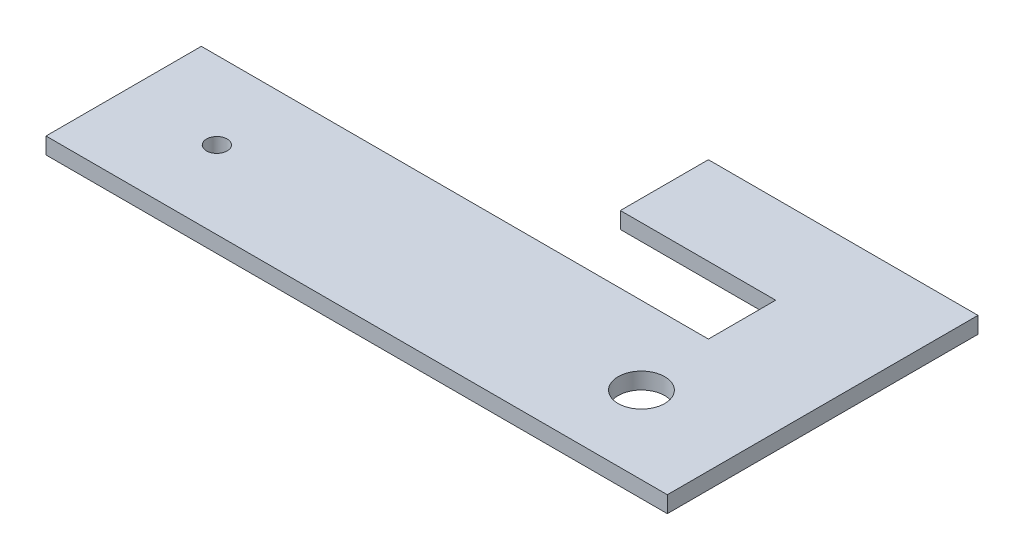
SolidWorks part; units mm, degrees
ref_plane "Front" through (0, 0, 0) normal (0, 0, 1) x (1, 0, 0)
ref_plane "Top" through (0, 0, 0) normal (0, 1, 0) x (1, 0, 0)
ref_plane "Right" through (0, 0, 0) normal (1, 0, 0) x (0, 0, -1)
sketch "Sketch1" plane through (0, 0, 0) normal (0, 1, 0) x (1, 0, 0)
  line L1 (0, 0) -> (120, 0)
  line L2 (0, 0) -> (0, 30)
  line L3 (0, 30) -> (120, 30)
  line L4 (120, 0) -> (120, 30)
  dimension "D1" = 120
  dimension "D2" = 30
extrude "Boss-Extrude1" add sketch "Sketch1" along normal blind 3.175
sketch "Sketch2" plane through (0, 3.175, 0) normal (0, 1, 0) x (1, 0, 0)
  line L0 (0, 30) -> (0, 0) construction
  line L1 (120, 30) -> (0, 30) construction
  line L2 (120, 0) -> (120, 30) construction
  circle A0 centre (18, 15) radius 2
  circle A1 centre (100, 15) radius 4.5
  dimension "D1" = 18
  dimension "D3" = 15
  dimension "D2" = 15
  dimension "D4" = 20
extrude "Cut-Extrude1" cut sketch "Sketch2" against normal blind 3.175
sketch "Sketch3" plane through (0, 0, -30) normal (0, 0, -1) x (-1, 0, 0)
  line L0 (-120, 0) -> (0, 0) construction
  line L1 (-97.9274, 0) -> (-120, 0)
  line L2 (-97.9274, 0) -> (-97.9274, 3.175)
  line L3 (-97.9274, 3.175) -> (-120, 3.175)
  line L4 (-120, 0) -> (-120, 3.175)
  line L5 (-120, 3.175) -> (-120, 0) construction
  line L6 (-120, 3.175) -> (0, 3.175) construction
extrude "Boss-Extrude2" add sketch "Sketch3" along normal blind 30
sketch "Sketch4" plane through (0, 3.175, 0) normal (0, 1, 0) x (1, 0, 0)
  line L0 (97.9274, 60) -> (120, 60) construction
  line L1 (97.9274, 60) -> (97.9274, 30) construction
  circle A0 centre (101.9274, 38) radius 1.3818
  dimension "D1" = 22
  dimension "D2" = 4
extrude "Cut-Extrude2" cut sketch "Sketch4" against normal blind 10
sketch "Sketch7" plane through (0, 3.175, 0) normal (0, 1, 0) x (1, 0, 0)
  circle A0 centre (101.9274, 38) radius 1.3818
extrude "Boss-Extrude4" add sketch "Sketch7" against normal blind 3.175
sketch "Sketch10" plane through (97.9274, 0, 0) normal (-1, 0, 0) x (0, 0, 1)
  line L0 (-60, 3.175) -> (-30, 3.175) construction
  line L1 (-60, 0) -> (-43, 0)
  line L2 (-60, 0) -> (-60, 3.175)
  line L3 (-60, 3.175) -> (-43, 3.175)
  line L4 (-43, 0) -> (-43, 3.175)
  dimension "D1" = 17
extrude "Boss-Extrude7" add sketch "Sketch10" along normal blind 30
